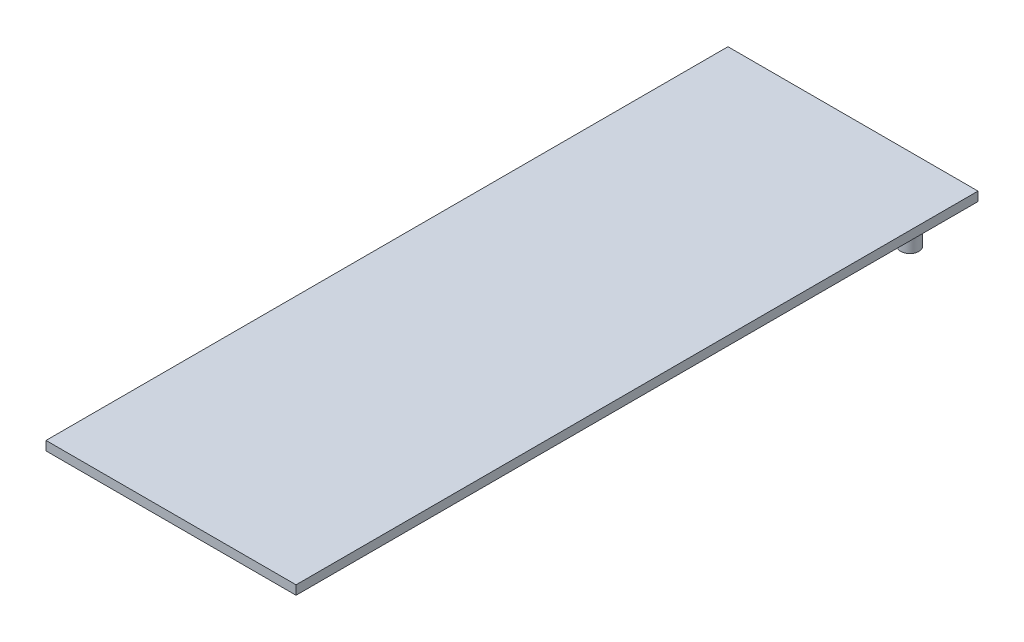
SolidWorks part; units mm, degrees
ref_plane "Front" through (0, 0, 0) normal (0, 0, 1) x (1, 0, 0)
ref_plane "Top" through (0, 0, 0) normal (0, 1, 0) x (1, 0, 0)
ref_plane "Right" through (0, 0, 0) normal (1, 0, 0) x (0, 0, -1)
ref_axis "X" through (-80.9, 0, 0) along (1, 0, 0)
ref_axis "Y" through (0, -50, 0) along (0, 1, 0)
ref_axis "Z" through (0, 0, -80.9) along (0, 0, 1)
sketch "Sketch1" plane through (0, 0, 0) normal (0, 1, 0) x (1, 0, 0)
  line L0 (-50, 0) -> (50, 0) construction
  circle A0 centre (-50, 0) radius 2
  circle A1 centre (50, 0) radius 2
  dimension "D2" = 4
  dimension "D1" = 100
extrude "Boss-Extrude1" add sketch "Sketch1" against normal blind 6
sketch "Sketch2" plane through (0, 0, 0) normal (0, 1, 0) x (1, 0, 0)
  line L0 (0, 0) -> (0, -65) construction
  line L1 (-55, 10) -> (55, 10)
  line L2 (-55, 10) -> (-55, -140)
  line L3 (-55, -140) -> (55, -140)
  line L4 (55, 10) -> (55, -140)
  line L5 (-55, 10) -> (55, -140) construction
  line L6 (-55, -140) -> (55, 10) construction
  point P4 (0, -65)
  dimension "D1" = 10
  dimension "D2" = 110
  dimension "D3" = 150
extrude "Boss-Extrude2" add sketch "Sketch2" along normal blind 2
sketch "Sketch3" plane through (0, 0, 0) normal (1, 0, 0) x (0, 0, -1)
  line L1 (122.025, 107.2329) -> (-274.9455, 107.2329)
  line L2 (122.025, 107.2329) -> (122.025, -88.1753)
  line L3 (122.025, -88.1753) -> (-274.9455, -88.1753)
  line L4 (-274.9455, 107.2329) -> (-274.9455, -88.1753)
  line L5 (122.025, 107.2329) -> (-274.9455, -88.1753) construction
  line L6 (122.025, -88.1753) -> (-274.9455, 107.2329) construction
  point P4 (-76.4602, 9.5288)
extrude "Cut-Extrude1" cut sketch "Sketch3" against normal through all
